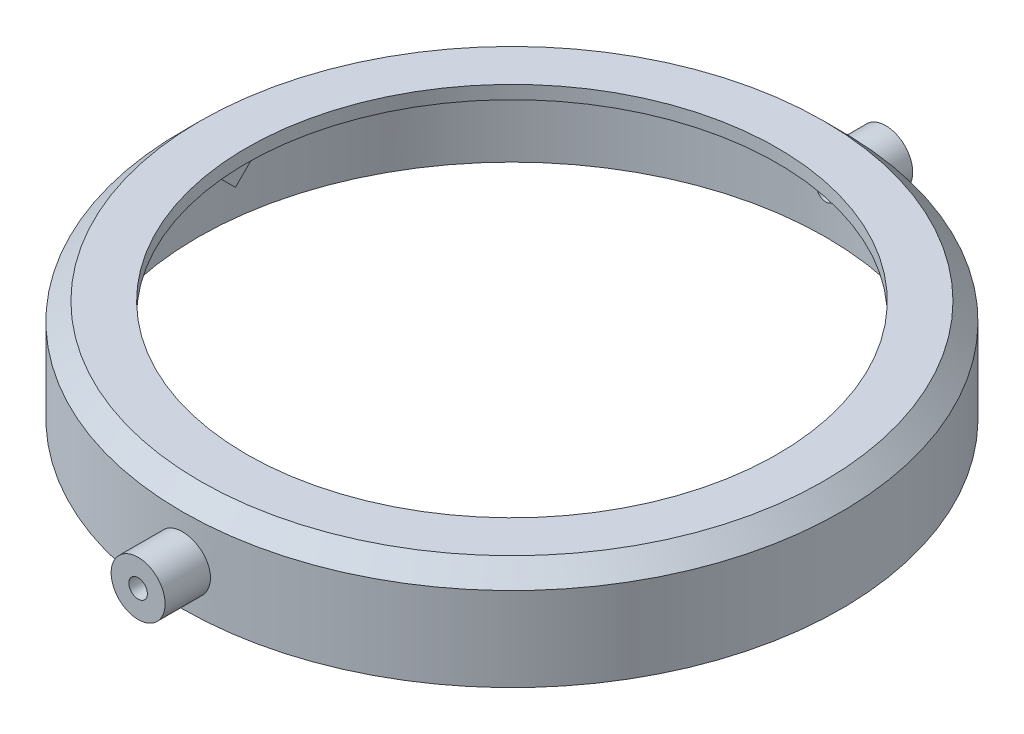
SolidWorks part; units mm, degrees
ref_plane "Front Plane" through (0, 0, 0) normal (0, 0, 1) x (1, 0, 0)
ref_plane "Top Plane" through (0, 0, 0) normal (0, 1, 0) x (1, 0, 0)
ref_plane "Right Plane" through (0, 0, 0) normal (1, 0, 0) x (0, 0, -1)
sketch "Sketch1" plane through (0, 0, 0) normal (0, 1, 0) x (1, 0, 0)
  line L0 (0, 0) -> (0, 13.7725) construction
  line L1 (0, 0) -> (-10.9504, 0) construction
  circle A0 centre (0, 0) radius 35.5
  circle A1 centre (0, 0) radius 35 construction
  circle A2 centre (0, 0) radius 37.25
  circle A3 centre (0, 0) radius 30
  dimension "D1" = 71
  dimension "D2" = 70
  dimension "D3" = 1.75
  dimension "D4" = 60
extrude "Boss-Extrude1" add sketch "Sketch1" against normal blind 10 contours A2 A0 region at (-36.1964, 0, 0)
extrude "Boss-Extrude2" add sketch "Sketch1<2>" along normal blind 1.5 contours A0 | A2 A0 region at (-34.4959, 0, 0) region at (-36.1964, 0, 0)
sketch "Sketch1<2>" plane through (0, 0, 0) normal (0, 1, 0) x (1, 0, 0) same geometry as "Sketch1"
chamfer "Chamfer1" distance 1.5 angle 45 1 edges at (0, 0, 35.5)
chamfer "Chamfer2" distance 2 angle 45 1 edges at (0, 1.5, 37.25)
ref_plane "Plane1" through (0, 0, 37.25) normal (0, 0, 1) x (1, 0, 0)
sketch "Sketch2" plane through (0, 0, 37.25) normal (0, 0, 1) x (1, 0, 0)
  line L0 (0, -0.5) -> (0, -10) construction
  line L1 (-37.25, -0.5) -> (37.25, -0.5) construction
  line L2 (-37.25, -10) -> (37.25, -10) construction
  circle A0 centre (0, -5.5) radius 1.05
  circle A1 centre (0, -5.5) radius 3.05
  dimension "D1" = 2.1
  dimension "D2" = 2
  dimension "D3" = 5
extrude "Cut-Extrude1" cut sketch "Sketch2" against normal blind 10 contours L0 A0 | A0 L0 region at (0.4456, -5.5, 37.25) region at (-0.4456, -5.5, 37.25)
extrude "Boss-Extrude4" add sketch "Sketch2<3>" along normal blind 5 and the other way blind 1 contours A1 L0 A0 | L0 A1 A0 region at (1.4086, -5.5, 37.25) region at (-1.4086, -5.5, 37.25)
sketch "Sketch2<3>" plane through (0, 0, 37.25) normal (0, 0, 1) x (1, 0, 0) same geometry as "Sketch2"
mirror "Mirror1" about plane through (0, 0, 0) normal (0, 0, 1) of "Boss-Extrude4", "Cut-Extrude1"
ref_plane "Plane2" through (37.25, 0, 0) normal (1, 0, 0) x (0, 0, -1)
sketch "tirangle" plane through (37.25, 0, 0) normal (1, 0, 0) x (0, 0, -1)
  line L0 (0, -0.5) -> (0, -13.8889) construction
  line L2 (2.5, -0.5) -> (-2.5, -0.5)
  line L6 (-2.5, -0.5) -> (0, -3)
  line L7 (-37.25, -0.5) -> (37.25, -0.5) construction
  line L8 (0, -3) -> (2.5, -0.5)
  dimension "D1" = 45
  dimension "D2" = 5
extrude "Boss-Extrude6" add sketch "tirangle" against normal blind 5 from offset 1 offset against normal yes
mirror "Mirror2" about plane through (0, 0, 0) normal (1, 0, 0) of "Boss-Extrude6"
